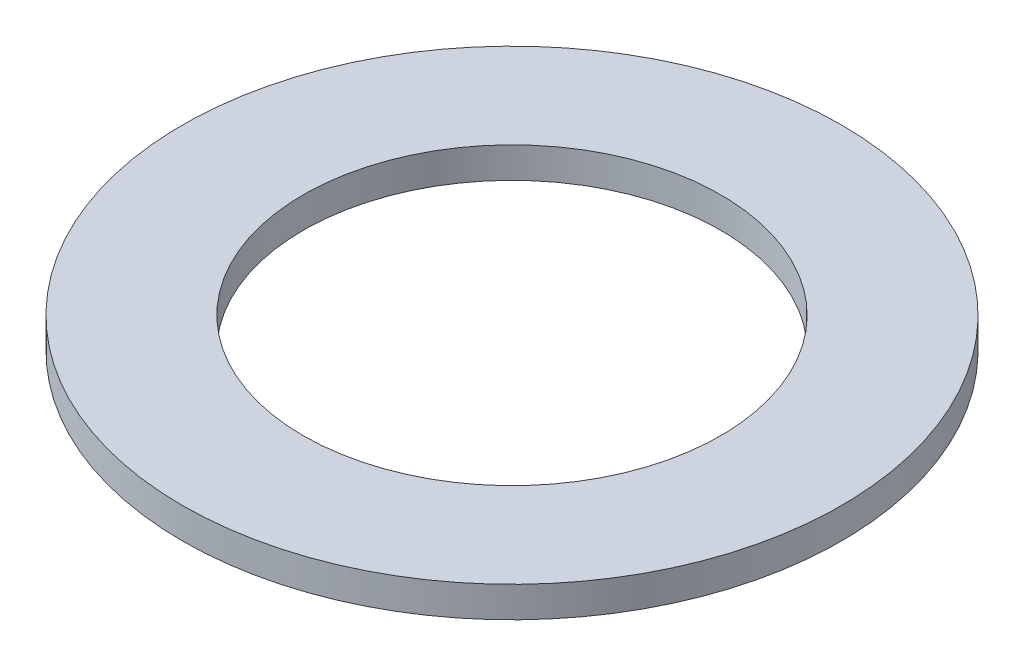
SolidWorks part; units mm, degrees
ref_plane "Front Plane" through (0, 0, 0) normal (0, 0, 1) x (1, 0, 0)
ref_plane "Top Plane" through (0, 0, 0) normal (0, 1, 0) x (1, 0, 0)
ref_plane "Right Plane" through (0, 0, 0) normal (1, 0, 0) x (0, 0, -1)
sketch "Sketch1" plane through (0, 0, 0) normal (0, 1, 0) x (1, 0, 0)
  circle A0 centre (0, 0) radius 75
  dimension "FLANGE_OD" = 150
extrude "Boss-Extrude1" add sketch "Sketch1" along normal blind 7
sketch "Sketch2" plane through (0, 0, 0) normal (0, 1, 0) x (1, 0, 0)
  circle A0 centre (0, 0) radius 47.5
  dimension "BORE_D" = 95
extrude "Cut-Extrude1" cut sketch "Sketch2" along normal through all
sketch "Sketch3" plane through (0, 7, 0) normal (0, 1, 0) x (1, 0, 0)
  circle A0 centre (0, 0) radius 27.8971 construction
  circle A1 centre (-27.8971, 0) radius 3.7739
  dimension "BOLT_D" = 7.5479
  dimension "BOLT_PCD" = 55.7941
extrude "Cut-Extrude2" cut sketch "Sketch3" against normal blind 6.1124 rebuild error yes
pattern_circular "CirPattern1" count 6 over 360 rebuild error yes
